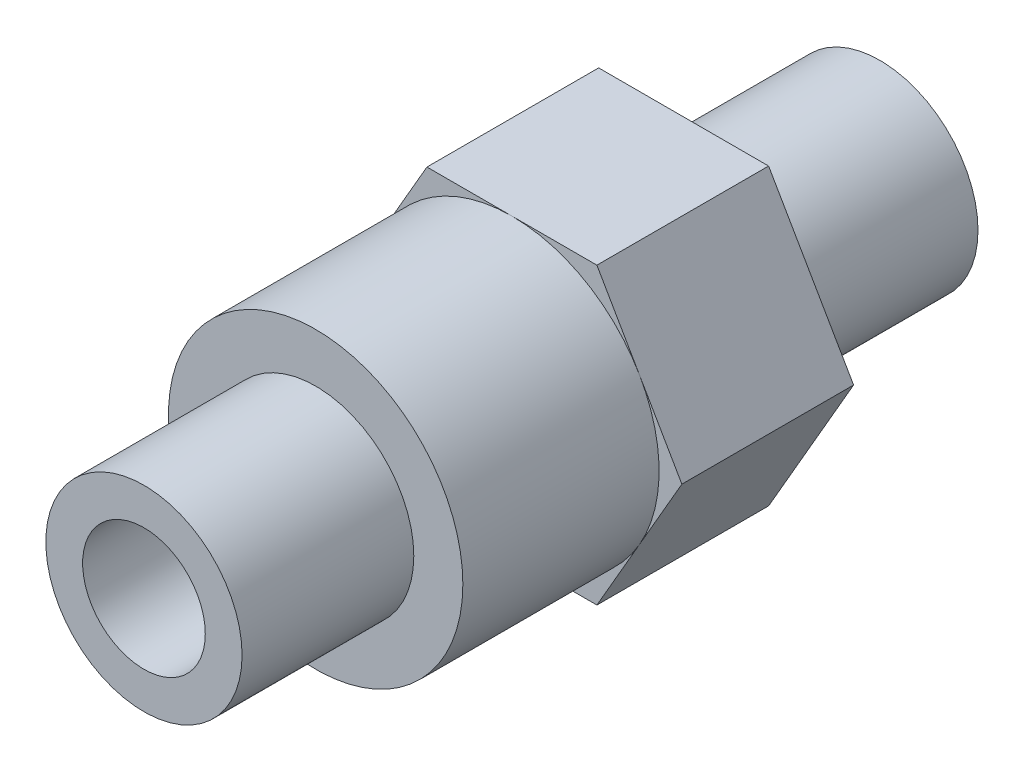
SolidWorks part; units mm, degrees
material "Brass"
ref_plane "Front Plane" through (0, 0, 0) normal (0, 0, 1) x (1, 0, 0)
ref_plane "Top Plane" through (0, 0, 0) normal (0, 1, 0) x (1, 0, 0)
ref_plane "Right Plane" through (0, 0, 0) normal (1, 0, 0) x (0, 0, -1)
sketch "Sketch1" plane through (0, 0, 0) normal (0, 0, 1) x (1, 0, 0)
  line L1 (6.9282, 0) -> (3.4641, 6)
  line L2 (3.4641, 6) -> (-3.4641, 6)
  line L3 (-3.4641, 6) -> (-6.9282, 0)
  line L4 (-6.9282, 0) -> (-3.4641, -6)
  line L5 (-3.4641, -6) -> (3.4641, -6)
  line L6 (3.4641, -6) -> (6.9282, 0)
  circle A0 centre (0, 0) radius 6
  circle A1 centre (0, 0) radius 2.5
  circle A2 centre (0, 0) radius 4
  dimension "D2" = 5
  dimension "D3" = 8
  dimension "D1" = 12
extrude "Boss-Extrude1" add sketch "Sketch1" against normal blind 7 contours A0 L2 L3 | A0 L1 L2 | A0 L6 L1 | A0 L5 L6 | A0 L4 L5 | A0 L3 L4 | A0 A2 region at (6.2014, 0, 0) region at (3.1007, 5.3706, 0) region at (5.6316, 1.509, 0) region at (3.1007, -5.3706, 0) region at (-3.1007, 5.3706, 0) region at (-3.1007, -5.3706, 0) region at (-6.2014, 0, 0)
extrude "Boss-Extrude2" add sketch "Sketch1<3>" against normal blind 15 contours A2 A1 region at (-3.8869, 0, 0)
sketch "Sketch1<3>" plane through (0, 0, 0) normal (0, 0, 1) x (1, 0, 0) same geometry as "Sketch1"
cosmetic thread "Cosmetic Thread2" parameters "D2"=6.619
extrude "Boss-Extrude3" add sketch "Sketch1<4>" along normal blind 8 contours A0 A2 region at (5.6316, 1.509, 0)
sketch "Sketch1<4>" plane through (0, 0, 0) normal (0, 0, 1) x (1, 0, 0) same geometry as "Sketch1"
extrude "Boss-Extrude4" add sketch "Sketch1<5>" along normal blind 15 contours A2 A1 region at (-3.8869, 0, 0)
sketch "Sketch1<5>" plane through (0, 0, 0) normal (0, 0, 1) x (1, 0, 0) same geometry as "Sketch1"
cosmetic thread "Cosmetic Thread1" parameters "D2"=6.619
